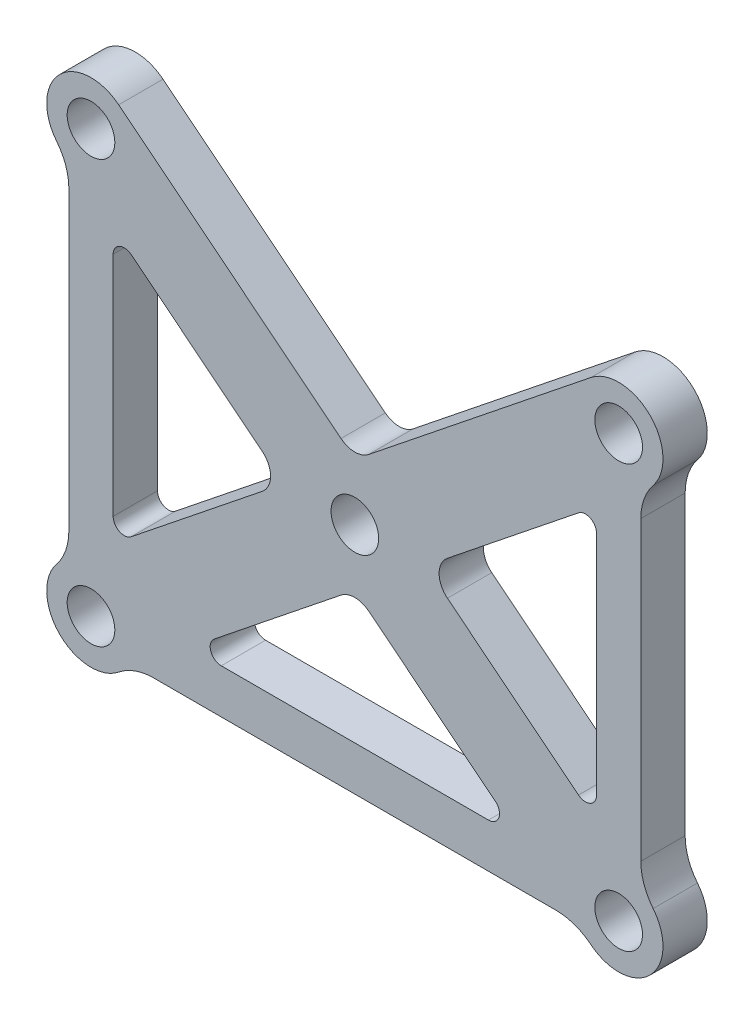
SolidWorks part; units mm, degrees
ref_plane "Front Plane" through (0, 0, 0) normal (0, 0, 1) x (1, 0, 0)
ref_plane "Top Plane" through (0, 0, 0) normal (0, 1, 0) x (1, 0, 0)
ref_plane "Right Plane" through (0, 0, 0) normal (1, 0, 0) x (0, 0, -1)
sketch "Sketch1" plane through (0, 0, 0) normal (0, 0, 1) x (1, 0, 0)
  line L0 (0, 0) -> (47.625, 38.1) construction
  line L1 (0, 38.1) -> (47.625, 0) construction
  line L2 (2.4988, -3.1235) -> (50.1238, 34.9765)
  line L3 (-2.4988, 34.9765) -> (45.1262, -3.1235)
  line L4 (-2.4988, 3.1235) -> (45.1262, 41.2235)
  line L5 (2.4988, 41.2235) -> (50.1238, 3.1235)
  line L6 (0, 0) -> (47.625, 0) construction
  line L7 (0, 38.1) -> (0, 0) construction
  line L8 (47.625, 38.1) -> (47.625, 0) construction
  line L9 (45.625, 38.1) -> (45.625, 2)
  line L10 (2, 2) -> (45.625, 2)
  line L11 (2, 38.1) -> (2, 2)
  line L12 (49.625, 38.1) -> (49.625, -2)
  line L13 (-2, -2) -> (49.625, -2)
  line L14 (-2, 38.1) -> (-2, -2)
  arc A0 (2.4988, -3.1235) -> (-2.4988, 3.1235) centre (0, 0) cw
  arc A1 (50.1238, 34.9765) -> (45.1262, 41.2235) centre (47.625, 38.1) ccw
  arc A2 (-2.4988, 34.9765) -> (2.4988, 41.2235) centre (0, 38.1) cw
  arc A3 (45.1262, -3.1235) -> (50.1238, 3.1235) centre (47.625, 0) ccw
  circle A4 centre (0, 0) radius 2.15
  circle A8 centre (23.8125, 19.05) radius 2.15
  circle A9 centre (0, 38.1) radius 2.15
  circle A10 centre (47.625, 38.1) radius 2.15
  circle A11 centre (47.625, 0) radius 2.15
  point P5 (23.8125, 19.05)
  dimension "D5" = 4.3
  dimension "D1" = 38.1
  dimension "D2" = 47.625
  dimension "D3" = 4
  dimension "D4" = 4
  dimension "D6" = 2
  dimension "D7" = 2
extrude "Boss-Extrude1" add sketch "Sketch1" along normal blind 4 contours A4 L13 L2 L10 L11 L4 L14 | L2 L13 L3 L10 | A11 L12 L5 L9 L10 L3 L13 | L3 L10 L9 L5 L2 | L4 L11 L10 L2 L3 | L5 L4 L3 L2 A8 | A9 L11 L3 L4 L5 A2 L14 | A10 L12 L2 A1 L4 L5 L9 | A11 L13 L3 A3 L5 L12 | A11 L13 L12 | A4 L14 L13 | A4 L14 L4 A0 L2 L13 | A10 L9 L2 L12 | L12 L2 L9 L5 | A9 L14 L3 L11 | L3 L14 L4 L11 region at (-3.0383, -2.4306, 0) region at (2.6452, 1.7023, 0) region at (23.8125, -0.0957, 0) region at (12.1855, 9.7865, 0) region at (45.2789, -2.1091, 0) region at (44.9798, 1.7023, 0) region at (-0.0766, 19.05, 0) region at (20.7134, 16.6168, 0) region at (35.4395, 9.7865, 0) region at (-1.655, -1.655, 0) region at (0.3187, 34.5439, 0) region at (10.2953, 30.1349, 0) region at (37.3297, 30.1349, 0) region at (49.28, -1.655, 0) region at (47.3063, 34.5439, 0) region at (47.7016, 19.05, 0)
fillet "Fillet1" radius 2 4 edges at (23.8125, 13.9275, 2) (30.2156, 19.05, 2) (17.4094, 19.05, 2) (23.8125, 24.1725, 2)
fillet "Fillet2" radius 5 6 edges at (-2, 34.5775, 2) (49.625, 34.5775, 2) (49.625, 3.5225, 2) (43.7219, -2, 2) (3.9031, -2, 2) (-2, 3.5225, 2)
fillet "Fillet3" radius 1 6 edges at (45.625, 6.7225, 2) (45.625, 31.3775, 2) (38.7219, 2, 2) (8.9031, 2, 2) (2, 6.7225, 2) (2, 31.3775, 2)
